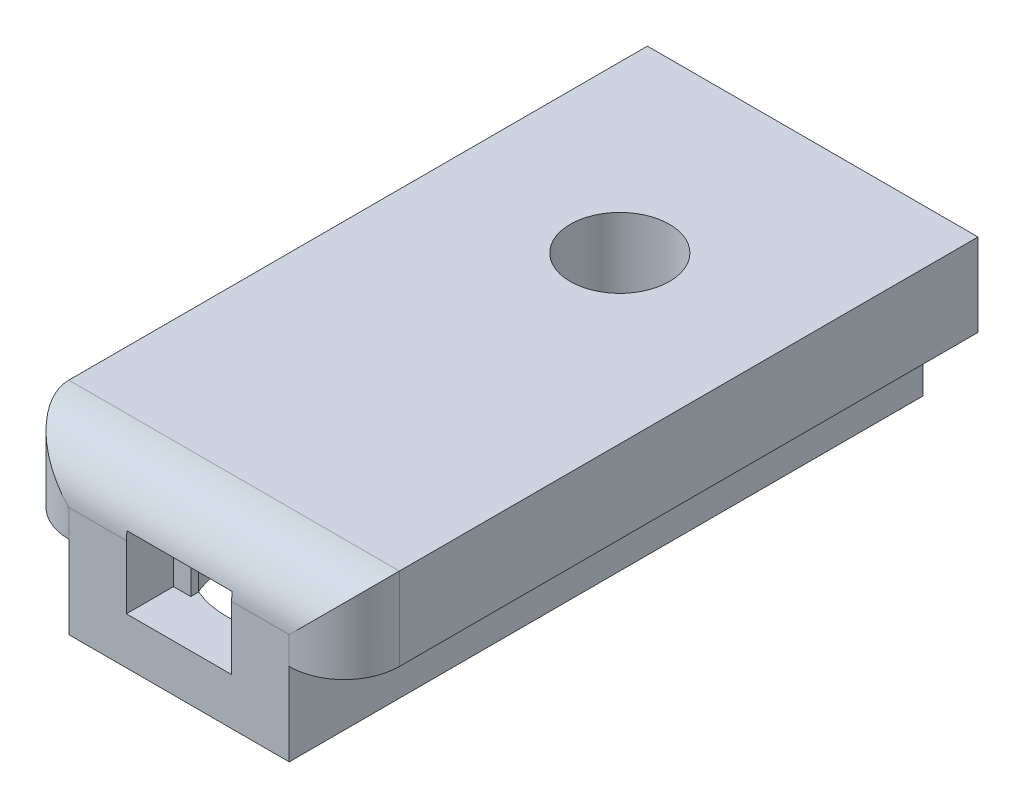
SolidWorks part; units mm, degrees
ref_plane "Front Plane" through (0, 0, 0) normal (0, 0, 1) x (1, 0, 0)
ref_plane "Top Plane" through (0, 0, 0) normal (0, 1, 0) x (1, 0, 0)
ref_plane "Right Plane" through (0, 0, 0) normal (1, 0, 0) x (0, 0, -1)
sketch "Sketch1" plane through (0, 0, 0) normal (0, 1, 0) x (1, 0, 0)
  line L1 (6, 11.5) -> (-6, 11.5)
  line L2 (6, 11.5) -> (6, -11.5)
  line L3 (6, -11.5) -> (-6, -11.5)
  line L4 (-6, 11.5) -> (-6, -11.5)
  line L5 (6, 11.5) -> (-6, -11.5) construction
  line L6 (6, -11.5) -> (-6, 11.5) construction
  point P0 (0, 0)
  dimension "D1" = 23
  dimension "D2" = 12
extrude "Boss-Extrude1" add sketch "Sketch1" along normal blind 6
sketch "Sketch2" plane through (0, 0, 11.5) normal (0, 0, 1) x (1, 0, 0)
  line L0 (0, 6) -> (0, 0) construction
  line L1 (-6, 6) -> (6, 6) construction
  line L2 (6, 3) -> (4, 3)
  line L3 (-6, 0) -> (-4, 0)
  line L4 (-6, 0) -> (-6, 3)
  line L5 (-6, 3) -> (-4, 3)
  line L6 (-4, 0) -> (-4, 3)
  line L7 (4, 0) -> (4, 3)
  line L8 (6, 0) -> (4, 0)
  line L9 (6, 0) -> (6, 3)
  dimension "D1" = 2
  dimension "D2" = 3
extrude "Cut-Extrude1" cut sketch "Sketch2" against normal through all
sketch "Sketch3" plane through (0, 0, 11.5) normal (0, 0, 1) x (1, 0, 0)
  line L0 (-4, 3) -> (4, 3) construction
  line L2 (1.91, 4.3) -> (-1.91, 4.3)
  line L3 (1.91, 4.3) -> (1.91, 1.7)
  line L4 (1.91, 1.7) -> (-1.91, 1.7)
  line L5 (-1.91, 4.3) -> (-1.91, 1.7)
  line L6 (1.91, 4.3) -> (-1.91, 1.7) construction
  line L7 (1.91, 1.7) -> (-1.91, 4.3) construction
  point P4 (0, 3)
  point P6 (0, 3)
  dimension "D1" = 3.82
  dimension "D2" = 2.6
extrude "Cut-Extrude2" cut sketch "Sketch3" against normal blind 1.71
sketch "Sketch4" plane through (0, 0, 9.79) normal (0, 0, 1) x (1, 0, 0)
  line L0 (-1.91, 3) -> (1.91, 3) construction
  line L1 (-1.91, 4.3) -> (-1.91, 1.7) construction
  line L2 (1.91, 1.7) -> (1.91, 4.3) construction
  line L3 (-1.91, 1.7) -> (1.91, 1.7) construction
  line L4 (-1.2833, 3.9) -> (1.2833, 3.9)
  line L5 (-1.2833, 3.9) -> (-1.2833, 1.7)
  line L6 (-1.2833, 1.7) -> (1.2833, 1.7)
  line L7 (1.2833, 3.9) -> (1.2833, 1.7)
  line L8 (-1.2833, 3.9) -> (1.2833, 1.7) construction
  line L9 (-1.2833, 1.7) -> (1.2833, 3.9) construction
  point P8 (0, 3)
  point P12 (0, 0)
  dimension "D1" = 2.2
extrude "Cut-Extrude3" cut sketch "Sketch4" against normal blind 3.1
sketch "Sketch5" plane through (0, 0, 0) normal (0, -1, 0) x (1, 0, 0)
  line L0 (0, 11.5) -> (0, 6.5) construction
  line L1 (-4, 11.5) -> (4, 11.5) construction
  circle A0 centre (0, 6.5) radius 3.265
  point P7 (0, 0)
  dimension "D2" = 6.53
  dimension "D1" = 5
extrude "Cut-Extrude4" cut sketch "Sketch5" against normal up to surface (3.9 mm away) up to face at (0, 3.9, 8.24)
fillet "Fillet1" radius 2 3 edges at (6, 4.5, 11.5) (0, 6, 11.5) (-6, 4.5, 11.5)
hole_wizard "CSK SLOT for M1.6 Countersunk Flat Head Screw1" positions "Sketch6" profile "Sketch7" size "M1.6" standard "ISO" slot yes end condition through all
sketch "Sketch6" plane through (0, 6, 0) normal (0, 1, 0) x (1, 0, 0)
  line L0 (6, 11.5) -> (-6, 11.5) construction
  line L1 (-6, 11.5) -> (-6, -9.5) construction
  point P0 (0, 4.5)
  dimension "D1" = 7
  dimension "D2" = 6
sketch "Sketch7" plane through (0, 6, -4.5) normal (1, 0, 0) x (0, 0, 1)
  line L0 (0, 0) -> (0, 6)
  line L1 (0, 6) -> (0.9, 6)
  line L2 (0.9, 6) -> (0.9, 4.9)
  line L3 (0.9, 4.9) -> (1.8, 4)
  line L4 (1.8, 4) -> (1.8, 0)
  line L6 (1.8, 0) -> (0, 0)
  line L7 (-0.9, 4.9) -> (-1.8, 4) construction
  line L11 (0, -6.35) -> (0, 107.95) construction
  dimension "Thru Hole Dia." = 1.8
  dimension "Thru Hole Depth" = 6
  dimension "C'Sink Dia." = 3.6
  dimension "C'Sink Angle" = 90
  dimension "Head Clearance" = 4
